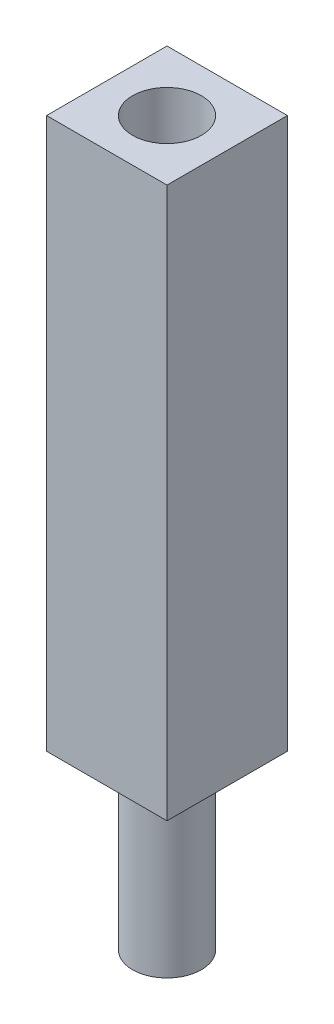
SolidWorks part; units mm, degrees
material "PLA"
ref_plane "Front Plane" through (0, 0, 0) normal (0, 0, 1) x (1, 0, 0)
ref_plane "Top Plane" through (0, 0, 0) normal (0, 1, 0) x (1, 0, 0)
ref_plane "Right Plane" through (0, 0, 0) normal (1, 0, 0) x (0, 0, -1)
sketch "Sketch1" plane through (0, 0, 0) normal (0, 1, 0) x (1, 0, 0)
  line L1 (-3.5, -3.5) -> (3.5, -3.5)
  line L2 (-3.5, -3.5) -> (-3.5, 3.5)
  line L3 (-3.5, 3.5) -> (3.5, 3.5)
  line L4 (3.5, -3.5) -> (3.5, 3.5)
  line L5 (-3.5, -3.5) -> (3.5, 3.5) construction
  line L6 (-3.5, 3.5) -> (3.5, -3.5) construction
  circle A2 centre (0, 0) radius 2
  dimension "D2" = 7
  dimension "D3" = 4
extrude "Boss-Extrude1" add sketch "Sketch1" along normal blind 10 contours A2 region at (0, 0, 0)
extrude "Boss-Extrude2" add sketch "Sketch1<3>" along normal blind 2 from surface contours L3 L4 L1 L2 starting at face at (0, 10, 2)
sketch "Sketch1<3>" plane through (0, 0, 0) normal (0, 1, 0) x (1, 0, 0) same geometry as "Sketch1"
extrude "Boss-Extrude3" add sketch "Sketch1<4>" along normal blind 30 from surface contours L1 L4 L3 L2 A2 region at (-3.401, 0, 0) starting at face at (0, 12, 0)
sketch "Sketch1<4>" plane through (0, 0, 0) normal (0, 1, 0) x (1, 0, 0) same geometry as "Sketch1"
